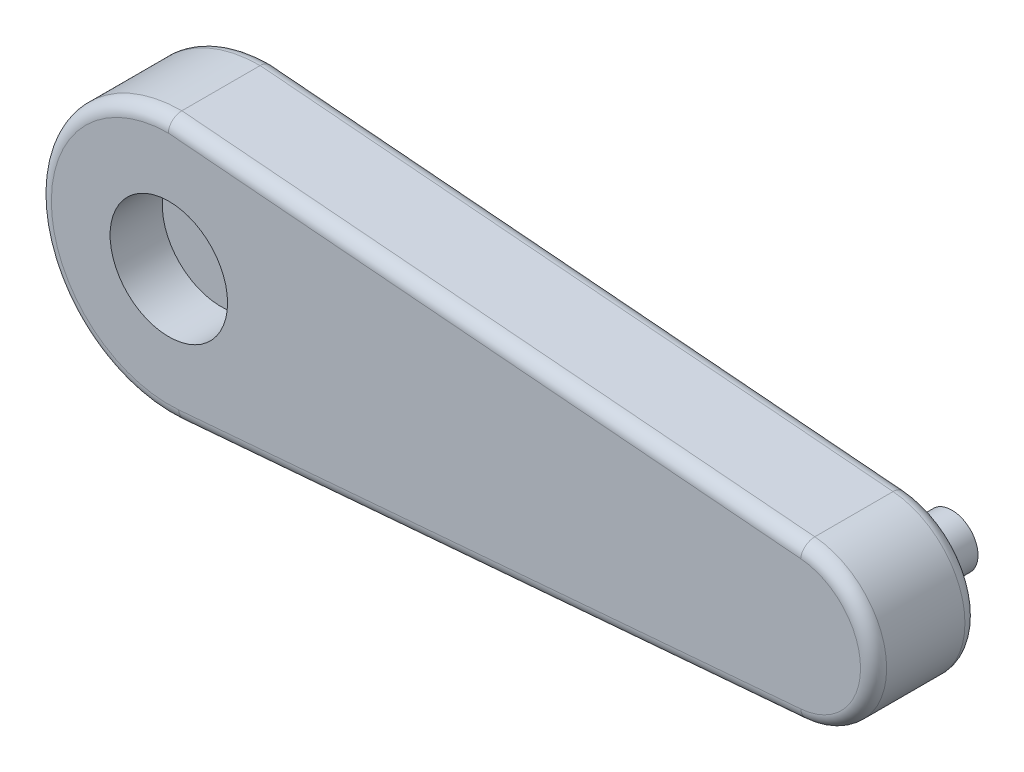
SolidWorks part; units mm, degrees
ref_plane "Front Plane" through (0, 0, 0) normal (0, 0, 1) x (1, 0, 0)
ref_plane "Top Plane" through (0, 0, 0) normal (0, 1, 0) x (1, 0, 0)
ref_plane "Right Plane" through (0, 0, 0) normal (1, 0, 0) x (0, 0, -1)
sketch "Sketch1" plane through (0, 0, 0) normal (0, 0, 1) x (1, 0, 0)
  line L0 (-53.1959, 0) -> (66.8041, 0) construction
  line L1 (-53.1959, 25) -> (68.0434, 14.9487)
  line L2 (-51.1125, -24.913) -> (68.0541, -14.9478)
  arc A0 (-49.0789, 24.6587) -> (-51.1125, -24.913) centre (-53.1959, 0) ccw
  arc A1 (68.0541, -14.9478) -> (68.0434, 14.9487) centre (66.8041, 0) ccw
  dimension "D2" = 50
  dimension "D3" = 30
  dimension "D1" = 120
extrude "Boss-Extrude1" add sketch "Sketch1" along normal blind 20 contours L2 A1 L1 A0 region at (-4.5582, -0.0184, 0)
sketch "Sketch2" plane through (0, 0, 0) normal (0, 0, -1) x (-1, 0, 0)
  circle A0 centre (-66.8041, 0) radius 5
  dimension "D1" = 10
extrude "Boss-Extrude2" add sketch "Sketch2" along normal blind 10
sketch "Sketch3" plane through (0, 0, 20) normal (0, 0, 1) x (1, 0, 0)
  circle A0 centre (-53.1959, 0) radius 11.25
  dimension "D1" = 22.5
extrude "Cut-Extrude1" cut sketch "Sketch3" against normal blind 10
fillet "Fillet1" radius 2.5 4 edges at (-78.1741, -1.0426, 20) (8.4708, -19.9304, 20) (81.8041, 0.0054, 20) (7.4238, 19.9744, 20)
fillet "Fillet2" radius 2.5 4 edges at (-78.1741, -1.0426, 0) (8.4708, -19.9304, 0) (81.8041, 0.0054, 0) (7.4238, 19.9744, 0)
